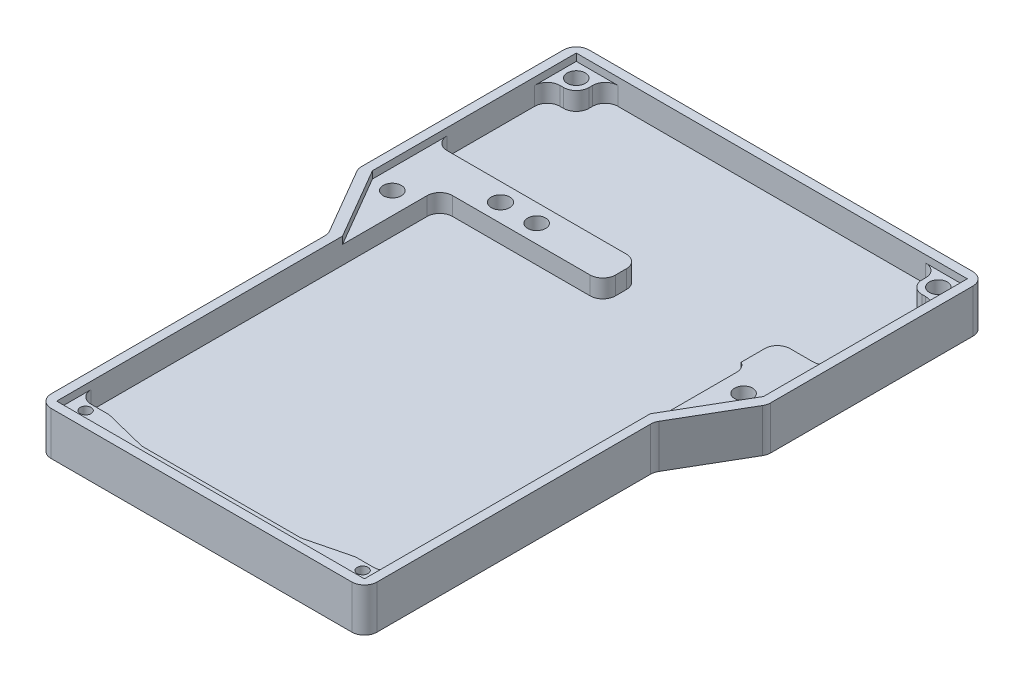
SolidWorks part; units mm, degrees
ref_plane "Front Plane" through (0, 0, 0) normal (0, 0, 1) x (1, 0, 0)
ref_plane "Top Plane" through (0, 0, 0) normal (0, 1, 0) x (1, 0, 0)
ref_plane "Right Plane" through (0, 0, 0) normal (1, 0, 0) x (0, 0, -1)
sketch "Sketch1" plane through (0, 0, 0) normal (0, 1, 0) x (1, 0, 0)
  line L0 (-57.5973, -8.4441) -> (-46.0973, -28.1941)
  line L1 (-46.0973, 51.8059) -> (43.9027, 51.8059)
  line L2 (-46.0973, 51.8059) -> (-46.0973, -108.1941)
  line L3 (-46.0973, -108.1941) -> (43.9027, -108.1941)
  line L4 (43.9027, 51.8059) -> (43.9027, -108.1941)
  line L5 (-57.5973, 51.8059) -> (55.4027, 51.8059)
  line L6 (-57.5973, 51.8059) -> (-57.5973, -8.4441)
  line L7 (-57.5973, -8.4441) -> (55.4027, -8.4441)
  line L8 (55.4027, 51.8059) -> (55.4027, -8.4441)
  line L9 (-57.5973, -8.4441) -> (-46.0973, -8.4441)
  line L10 (-46.0973, -8.4441) -> (-46.0973, -28.1941)
  line L11 (43.9027, -28.1941) -> (43.9027, -8.4441)
  line L12 (43.9027, -8.4441) -> (55.4027, -8.4441)
  line L13 (43.9027, -28.1941) -> (55.4027, -8.4441)
  point P12 (-1.0973, 51.8059)
  point P13 (-1.0973, 51.8059)
  dimension "D1" = 90
  dimension "D2" = 160
  dimension "D3" = 99.75
  dimension "D4" = 113
extrude "Boss-Extrude1" add sketch "Sketch1" along normal blind 5 contours L8 L5 L4 L7 | L2 L7 L4 L1 | L6 L7 L2 L5 | L7 L0 L2 | L7 L2 L3 L4 | L4 L13 L7 | L6 L5 L8 L7 | L12 L11 L13 region at (-49.9306, 0, 15.0275) region at (-51.8473, 0, -21.6809) region at (-1.0973, 0, 58.3191) region at (-1.0973, 0, -21.6809) region at (47.736, 0, 15.0275) region at (49.6527, 0, -21.6809)
sketch "Sketch2" plane through (0, 5, 0) normal (0, 1, 0) x (1, 0, 0)
  line L0 (-46.0973, -108.1941) -> (43.9027, -108.1941)
  line L9 (43.9027, -108.1941) -> (43.9027, -28.1941)
  line L10 (43.9027, -28.1941) -> (55.4027, -8.4441)
  line L11 (55.4027, -8.4441) -> (55.4027, 51.8059)
  line L12 (55.4027, 51.8059) -> (-57.5973, 51.8059)
  line L13 (-57.5973, 51.8059) -> (-57.5973, -8.4441)
  line L14 (-57.5973, -8.4441) -> (-46.0973, -28.1941)
  line L15 (-46.0973, -28.1941) -> (-46.0973, -108.1941)
  line L16 (-43.5973, -105.6941) -> (41.4027, -105.6941)
  line L17 (41.4027, -105.6941) -> (41.4027, -26.7384)
  line L18 (41.4027, -26.7384) -> (52.9027, -6.9884)
  line L19 (52.9027, -6.9884) -> (52.9027, 49.3059)
  line L20 (52.9027, 49.3059) -> (-55.0973, 49.3059)
  line L21 (-55.0973, 49.3059) -> (-55.0973, -6.9884)
  line L22 (-55.0973, -6.9884) -> (-43.5973, -26.7384)
  line L23 (-43.5973, -26.7384) -> (-43.5973, -105.6941)
  line L24 (43.9027, -28.1941) -> (41.4027, -28.1941)
  line L25 (41.4027, -28.1941) -> (41.4027, -26.7384)
  line L26 (43.9027, -28.1941) -> (41.4027, -26.7384)
  line L27 (52.9027, -6.9884) -> (55.4027, -6.9884)
  line L28 (55.4027, -6.9884) -> (55.4027, -8.4441)
  line L29 (52.9027, -6.9884) -> (55.4027, -8.4441)
  line L30 (55.4027, -6.9884) -> (55.4027, -8.4441)
  line L31 (-55.0973, -6.9884) -> (-57.5973, -6.9884)
  line L32 (-57.5973, -6.9884) -> (-57.5973, -8.4441)
  line L33 (-57.5973, -8.4441) -> (-55.0973, -6.9884)
  line L34 (-43.5973, -26.7384) -> (-46.0973, -28.1941)
  line L35 (-46.0973, -28.1941) -> (-43.5973, -28.1941)
  line L36 (-43.5973, -28.1941) -> (-43.5973, -26.7384)
  line L37 (-57.5973, -6.9884) -> (-57.5973, -8.4441)
  dimension "D1" = 2.5
  dimension "D2" = 2.5
  dimension "D3" = 2.5
  dimension "D4" = 90
  dimension "D5" = 90
  dimension "D6" = 2.5
  dimension "D7" = 2.5
  dimension "D8" = 90
  dimension "D9" = 90
extrude "Boss-Extrude2" add sketch "Sketch2" along normal blind 7 contours L35 L15 L0 L9 L24 L17 L16 L23 | L29 L18 L26 L10 | L24 L26 L17 | L27 L29 L11 | L31 L21 L20 L19 L27 L11 L12 L13 | L34 L35 L23 | L34 L22 L33 L14 | L13 L33 L31 region at (-44.8932, 5, 68.1941) region at (-50.5973, 5, 17.5913) region at (-44.4306, 5, 27.7089) region at (48.4027, 5, 17.5913) region at (42.236, 5, 27.7089) region at (-56.764, 5, 7.4737) region at (54.5694, 5, 7.4737) region at (-56.3235, 5, -22.4087)
sketch "Sketch3" plane through (0, 5, 0) normal (0, 1, 0) x (1, 0, 0)
  line L0 (41.4027, -105.6941) -> (41.4027, 49.3059) construction
  line L1 (-43.5973, -105.6941) -> (41.4027, -105.6941)
  line L2 (-43.5973, -105.6941) -> (-43.5973, -99.6941)
  line L3 (-43.5973, -99.6941) -> (41.4027, -99.6941)
  line L4 (41.4027, -105.6941) -> (41.4027, -99.6941)
  line L5 (-35.0973, -99.6941) -> (-23.0973, -102.6941)
  line L6 (-23.0973, -102.6941) -> (20.9027, -102.6941)
  line L7 (20.9027, -102.6941) -> (32.9027, -99.6941)
  line L8 (-35.0973, -99.6941) -> (-35.0973, -105.6941)
  line L9 (-35.0973, -105.6941) -> (32.9027, -105.6941)
  line L10 (32.9027, -105.6941) -> (32.9027, -99.6941)
  line L11 (55.4027, 51.8059) -> (-57.5973, 51.8059) construction
  line L12 (-55.0973, 49.3059) -> (-47.0973, 49.3059)
  line L13 (-55.0973, 49.3059) -> (-55.0973, 41.3059)
  line L14 (-55.0973, 41.3059) -> (-47.0973, 41.3059)
  line L15 (-47.0973, 49.3059) -> (-47.0973, 41.3059)
  line L16 (52.9027, 49.3059) -> (44.9027, 49.3059)
  line L17 (52.9027, 49.3059) -> (52.9027, 41.3059)
  line L18 (52.9027, 41.3059) -> (44.9027, 41.3059)
  line L19 (44.9027, 49.3059) -> (44.9027, 41.3059)
  circle A0 centre (-39.3473, -101.9441) radius 1.5
  circle A1 centre (37.1527, -101.9441) radius 1.5
  circle A2 centre (-51.0973, 45.3059) radius 2.5
  circle A3 centre (48.9027, 45.3059) radius 2.5
  point P32 (-55.0973, 45.3059)
  point P33 (-51.0973, 41.3059)
  point P34 (48.9027, 41.3059)
  point P35 (44.9027, 45.3059)
  dimension "D4" = 3
  dimension "D7" = 3
  dimension "D17" = 5
  dimension "D18" = 5
  dimension "D1" = 6
  dimension "D2" = 4.25
  dimension "D3" = 3.75
  dimension "D5" = 76.5
  dimension "D6" = 4.25
  dimension "D8" = 12
  dimension "D9" = 12
  dimension "D10" = 3
  dimension "D11" = 8.5
  dimension "D12" = 8.5
  dimension "D13" = 8
  dimension "D14" = 8
  dimension "D15" = 8
  dimension "D16" = 8
  dimension "D19" = 6.5
extrude "Boss-Extrude3" add sketch "Sketch3" along normal blind 5 contours L8 L3 A0 | L1 L10 L7 L6 L5 L8 | L10 L3 A1 | L13 L12 L15 L14 | L17 L16 L19 L18 | A2 | A3 region at (-43.4933, 5, 102.6941) region at (-1.0973, 5, 103.8191) region at (33.0067, 5, 102.6941)
sketch "Sketch4" plane through (0, 5, 0) normal (0, 1, 0) x (1, 0, 0)
  line L0 (-43.5973, 49.3059) -> (-43.5973, -99.6941) construction
  line L1 (-43.5973, 10.1309) -> (1.4027, 10.1309)
  line L2 (-43.5973, 10.1309) -> (-43.5973, 0.1309)
  line L3 (-43.5973, 0.1309) -> (1.4027, 0.1309)
  line L4 (1.4027, 10.1309) -> (1.4027, 0.1309)
  line L5 (41.4027, 49.3059) -> (-43.5973, 49.3059) construction
  line L6 (41.4027, -99.6941) -> (41.4027, 49.3059) construction
  line L7 (1.4027, 10.1309) -> (-43.5973, 10.1309)
  line L8 (1.4027, 10.1309) -> (1.4027, 49.3059)
  line L9 (1.4027, 49.3059) -> (-43.5973, 49.3059)
  line L10 (-43.5973, 10.1309) -> (-43.5973, 49.3059)
  line L11 (39.6145, 10.1309) -> (41.4027, 10.1309)
  line L12 (39.6145, 10.1309) -> (39.6145, 0.1309)
  line L13 (39.6145, 0.1309) -> (41.4027, 0.1309)
  line L14 (41.4027, 10.1309) -> (41.4027, 0.1309)
  line L15 (-55.0973, 49.3059) -> (-55.0973, -6.9884) construction
  line L16 (-43.5973, 0.1309) -> (-55.0973, 0.1309)
  line L17 (-43.5973, 0.1309) -> (-43.5973, 10.1309)
  line L18 (-43.5973, 10.1309) -> (-55.0973, 10.1309)
  line L19 (-55.0973, 0.1309) -> (-55.0973, 10.1309)
  line L20 (52.9027, -6.9884) -> (52.9027, 49.3059) construction
  line L21 (41.4027, 10.1309) -> (52.9027, 10.1309)
  line L22 (41.4027, 10.1309) -> (41.4027, 0.1309)
  line L23 (41.4027, 0.1309) -> (52.9027, 0.1309)
  line L24 (52.9027, 10.1309) -> (52.9027, 0.1309)
  line L25 (-43.5973, -26.7384) -> (-43.5973, 0.1309)
  line L26 (-55.0973, 0.1309) -> (-55.0973, -6.9884)
  line L27 (-55.0973, -6.9884) -> (-43.5973, -26.7384)
  line L28 (-43.5973, 0.1309) -> (-55.0973, 0.1309)
  line L29 (41.4027, -26.7384) -> (41.4027, 0.1309)
  line L30 (52.9027, 0.1309) -> (41.4027, 0.1309)
  line L31 (52.9027, 0.1309) -> (52.9027, -6.9884)
  line L32 (52.9027, -6.9884) -> (52.8628, -7.0199)
  line L33 (41.4027, -26.7384) -> (52.9027, -6.9884)
  circle A0 centre (-31.8473, 5.1309) radius 2.5
  circle A1 centre (-21.8473, 5.1309) radius 2.5
  dimension "D3" = 5
  dimension "D4" = 5
  dimension "D1" = 11.75
  dimension "D2" = 21.75
  dimension "D5" = 10
  dimension "D6" = 5
  dimension "D7" = 5
  dimension "D8" = 44.175
  dimension "D9" = 45
extrude "Boss-Extrude4" add sketch "Sketch4" along normal up to surface (5 mm away) contours L4 L1 L3 A1 A0 | L26 L27 L25 L16 | L29 L33 L31 L23 | L12 L11 L14 L13 | L17 L16 L19 L18 | L22 L21 L24 L23 region at (-21.0973, 5, -9.6699) region at (-48.2336, 5, 9.3226) region at (46.039, 5, 9.3226) up to face at (-51.0973, 10, -45.3059)
sketch "Sketch5" plane through (0, 5, 0) normal (0, 1, 0) x (1, 0, 0)
  line L0 (-55.0973, 10.1309) -> (-55.0973, -6.9884) construction
  line L1 (52.9027, -6.9884) -> (52.9027, 10.1309) construction
  circle A0 centre (-21.8473, 5.1309) radius 2.5
  circle A1 centre (-31.8473, 5.1309) radius 2.5593
  circle A2 centre (-39.3473, -101.9441) radius 1.5
  circle A3 centre (37.1527, -101.9441) radius 1.5
  circle A4 centre (-51.0973, 45.3059) radius 2.5
  circle A5 centre (48.9027, 45.3059) radius 2.5
  circle A6 centre (-49.5973, -6.9884) radius 2.5
  circle A7 centre (47.4027, -6.9884) radius 2.5
  point P26 (0, 0)
  point P28 (0, 0)
  point P30 (0, 0)
  dimension "D1" = 5
  dimension "D2" = 5
  dimension "D3" = 5.5
  dimension "D4" = 5.5
extrude "Cut-Extrude1" cut sketch "Sketch5" against normal through all both and the other way through all
fillet "Fillet1" radius 3.5 27 edges at (-46.0973, 6, 28.1941) (-57.5973, 6, 8.4441) (-57.5973, 6, -51.8059) (55.4027, 6, -51.8059) (55.4027, 6, 8.4441) (43.9027, 6, 28.1941) (-55.0973, 7.5, -41.3059) (-47.0973, 7.5, -49.3059) (-47.0973, 7.5, -41.3059) (44.9027, 7.5, -49.3059) (44.9027, 7.5, -41.3059) (52.9027, 7.5, -41.3059) (-55.0973, 7.5, -10.1309) (-43.5973, 7.5, -0.1309) (1.4027, 7.5, -10.1309) (1.4027, 7.5, -0.1309) (52.9027, 7.5, -10.1309) (39.6145, 7.5, -10.1309) (41.4027, 7.5, -0.1309) (-46.0973, 6, 108.1941) (43.9027, 6, 108.1941) (41.4027, 7.5, 99.6941) (32.9027, 7.5, 99.6941) (20.9027, 7.5, 102.6941) (-23.0973, 7.5, 102.6941) (-43.5973, 7.5, 99.6941) (-35.0973, 7.5, 99.6941)
